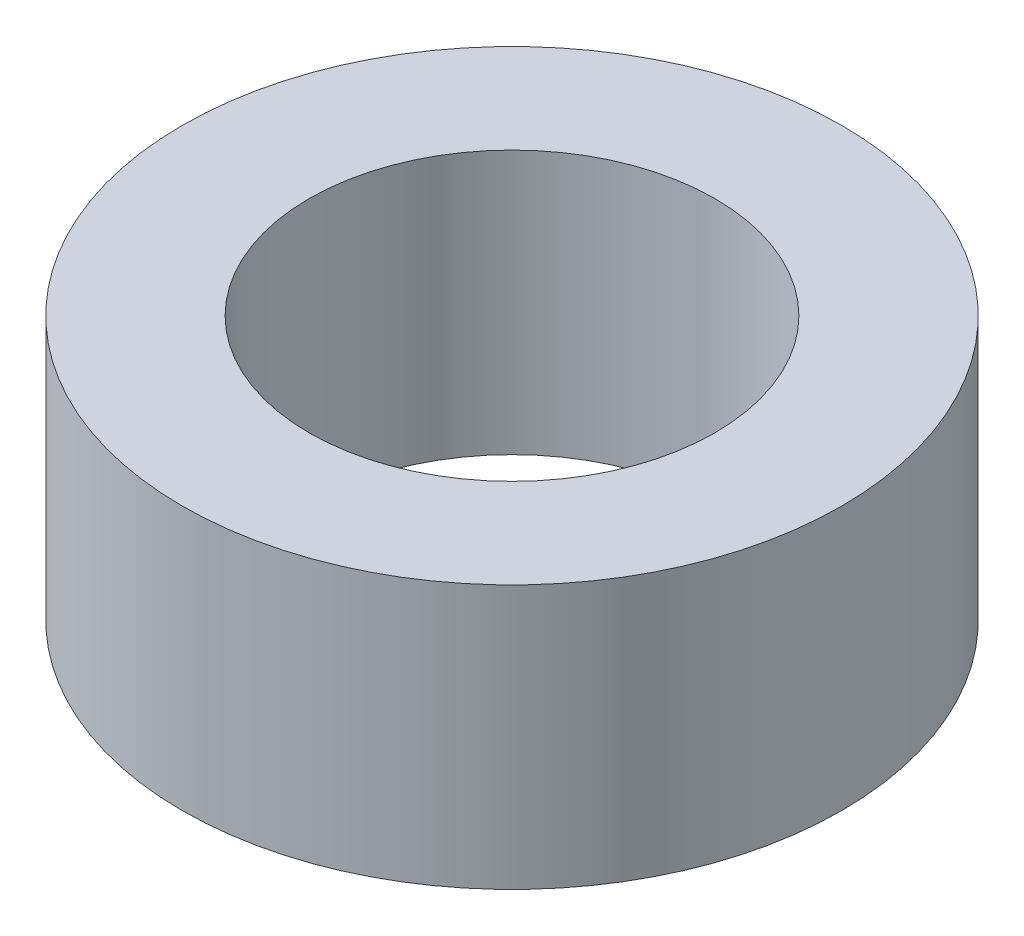
SolidWorks part; units mm, degrees
ref_plane "Front Plane" through (0, 0, 0) normal (0, 0, 1) x (1, 0, 0)
ref_plane "Top Plane" through (0, 0, 0) normal (0, 1, 0) x (1, 0, 0)
ref_plane "Right Plane" through (0, 0, 0) normal (1, 0, 0) x (0, 0, -1)
sketch "Sketch1" plane through (0, 0, 0) normal (0, 1, 0) x (1, 0, 0)
  circle A0 centre (0, 0) radius 32.5
  dimension "FLANGE_OD" = 65
extrude "Boss-Extrude1" add sketch "Sketch1" along normal blind 26
sketch "Sketch2" plane through (0, 0, 0) normal (0, 1, 0) x (1, 0, 0)
  circle A0 centre (0, 0) radius 20
  dimension "BORE_D" = 40
extrude "Cut-Extrude1" cut sketch "Sketch2" along normal through all
sketch "Sketch3" plane through (0, 26, 0) normal (0, 1, 0) x (1, 0, 0)
  circle A0 centre (0, 0) radius 14.6065 construction
  circle A1 centre (-14.6065, 0) radius 1.7835
  dimension "BOLT_D" = 3.567
  dimension "BOLT_PCD" = 29.213
extrude "Cut-Extrude2" cut sketch "Sketch3" against normal blind 25.6819 rebuild error yes
pattern_circular "CirPattern1" count 6 over 360 rebuild error yes
